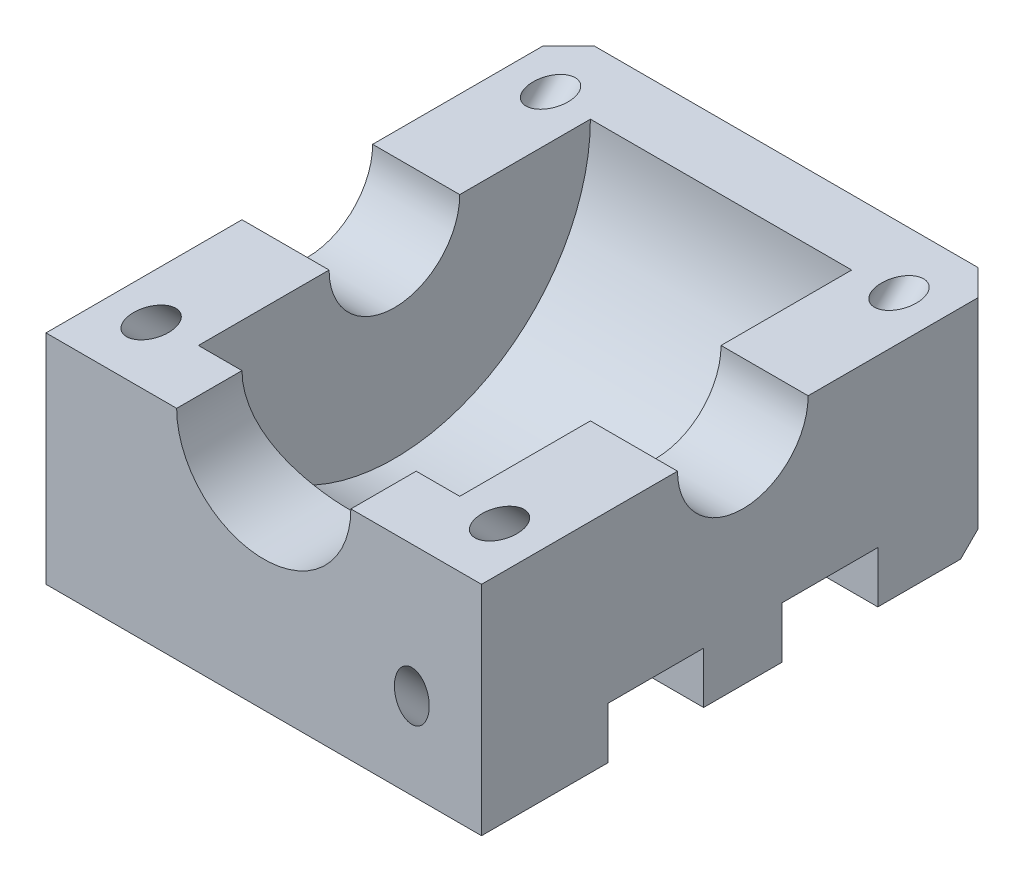
SolidWorks part; units mm, degrees
ref_plane "Front Plane" through (0, 0, 0) normal (0, 0, 1) x (1, 0, 0)
ref_plane "Top Plane" through (0, 0, 0) normal (0, 1, 0) x (1, 0, 0)
ref_plane "Right Plane" through (0, 0, 0) normal (1, 0, 0) x (0, 0, -1)
sketch "Sketch1" plane through (0, 0, 0) normal (0, 1, 0) x (1, 0, 0)
  line L1 (-25, 30) -> (25, 30)
  line L2 (-25, 30) -> (-25, -30)
  line L3 (-25, -30) -> (25, -30)
  line L4 (25, 30) -> (25, -30)
  line L5 (-25, 30) -> (25, -30) construction
  line L6 (-25, -30) -> (25, 30) construction
  point P0 (0, 0)
  dimension "D1" = 50
  dimension "D2" = 60
extrude "Boss-Extrude1" add sketch "Sketch1" along normal blind 25
sketch "Sketch2" plane through (-25, 0, 0) normal (-1, 0, 0) x (0, 0, 1)
  line L3 (-30, 25) -> (30, 25) construction
  line L6 (-30, 25) -> (-30, 0) construction
  circle A1 centre (0, 25) radius 22.5
  dimension "D1" = 45
  dimension "D2" = 7.5
extrude "Cut-Extrude1" cut sketch "Sketch2" against normal blind 30 from offset 10 offset against normal yes
sketch "Sketch3" plane through (-25, 0, 0) normal (-1, 0, 0) x (0, 0, 1)
  line L0 (-30, 25) -> (30, 25) construction
  line L1 (30, 25) -> (30, 0) construction
  circle A0 centre (0, 25) radius 7.5
  dimension "D1" = 15
  dimension "D2" = 30
extrude "Cut-Extrude2" cut sketch "Sketch3" against normal through all
sketch "Sketch4" plane through (0, 0, 30) normal (0, 0, 1) x (1, 0, 0)
  line L0 (-25, 25) -> (25, 25) construction
  circle A0 centre (0, 25) radius 10
  dimension "D1" = 20
extrude "Cut-Extrude3" cut sketch "Sketch4" against normal blind 10
sketch "Sketch5" plane through (0, 0, 0) normal (0, -1, 0) x (1, 0, 0)
  line L0 (-25, -30) -> (-25, 30) construction
  line L1 (25, -30) -> (-25, -30) construction
  circle A0 centre (-10, 20) radius 1.75
  circle A1 centre (10, 20) radius 1.75
  circle A2 centre (-10, -20) radius 1.75
  circle A3 centre (10, -20) radius 1.75
  dimension "D1" = 3.5
  dimension "D2" = 3.5
  dimension "D3" = 3.5
  dimension "D4" = 3.5
  dimension "D5" = 20
  dimension "D6" = 15
  dimension "D7" = 20
  dimension "D8" = 15
  dimension "D9" = 40
  dimension "D10" = 40
  dimension "D11" = 10
  dimension "D12" = 10
extrude "Cut-Extrude4" cut sketch "Sketch5" against normal blind 10
chamfer "Chamfer1" distance 5 angle 45 1 edges at (0, 0, -30)
sketch "Sketch6" plane through (0, 0, -30) normal (0, 0, -1) x (-1, 0, 0)
  line L0 (25, 25) -> (25, 5) construction
  line L1 (25, 0) -> (-25, 0) construction
  circle A0 centre (-20, 15) radius 2
  circle A1 centre (20, 15) radius 2
  dimension "D1" = 4
  dimension "D2" = 4
  dimension "D3" = 40
  dimension "D4" = 5
  dimension "D5" = 15
  dimension "D6" = 15
extrude "Cut-Extrude5" cut sketch "Sketch6" against normal blind 10
sketch "Sketch7" plane through (25, 0, 0) normal (1, 0, 0) x (0, 0, -1)
  line L0 (-30, 0) -> (25, 0) construction
  line L1 (-4.5, 0) -> (-15.5, 0)
  line L2 (-4.5, 0) -> (-4.5, 5.9067)
  line L3 (-4.5, 5.9067) -> (-15.5, 5.9067)
  line L4 (-15.5, 0) -> (-15.5, 5.9067)
  line L5 (30, 25) -> (30, 5) construction
  line L6 (15.5, 0) -> (4.5, 0)
  line L7 (15.5, 0) -> (15.5, 5.9067)
  line L8 (15.5, 5.9067) -> (4.5, 5.9067)
  line L9 (4.5, 0) -> (4.5, 5.9067)
  dimension "D1" = 14.5
  dimension "D2" = 11
  dimension "D3" = 9
  dimension "D4" = 11
extrude "Cut-Extrude6" cut sketch "Sketch7" against normal blind 9
chamfer "Chamfer2" distance 5 angle 45 2 edges at (16, 5.9067, -10) (16, 5.9067, 10)
mirror "Mirror1" about plane through (0, 0, 0) normal (1, 0, 0) of "Chamfer2", "Cut-Extrude6"
chamfer "Chamfer3" distance 3 angle 45 2 edges at (25, 15, -30) (-25, 15, -30)
ref_plane "Plane1" through (0, -2.5, -2.5) normal (0, 0.7071, 0.7071) x (1, 0, 0)
sketch "Sketch10" plane through (0, -2.5, -2.5) normal (0, 0.7071, 0.7071) x (1, 0, 0)
  line L0 (-25, 12.3744) -> (-25, -3.5355) construction
  line L1 (-25, -3.5355) -> (-10, -3.5355) construction
  circle A0 centre (-20, 1.4645) radius 2
  circle A1 centre (20, 1.4645) radius 2
  dimension "D1" = 4
  dimension "D3" = 4
  dimension "D2" = 40
  dimension "D4" = 5
  dimension "D5" = 5
extrude "Cut-Extrude8" cut sketch "Sketch10" along normal through all from offset 25
mirror "Mirror2" about plane through (0, 0, 0) normal (0, 0, 1) of "Cut-Extrude8"
sketch "Sketch11" plane through (0, -2.5, -2.5) normal (0, 0.7071, 0.7071) x (1, 0, 0)
  line L0 (25, -3.5355) -> (25, -21.2132) construction
  line L1 (-25, -21.2132) -> (25, -21.2132) construction
  circle A0 centre (17, -14.2132) radius 2
  dimension "D3" = 4
  dimension "D1" = 8
  dimension "D2" = 7
extrude "Cut-Extrude9" cut sketch "Sketch11" along normal through all
